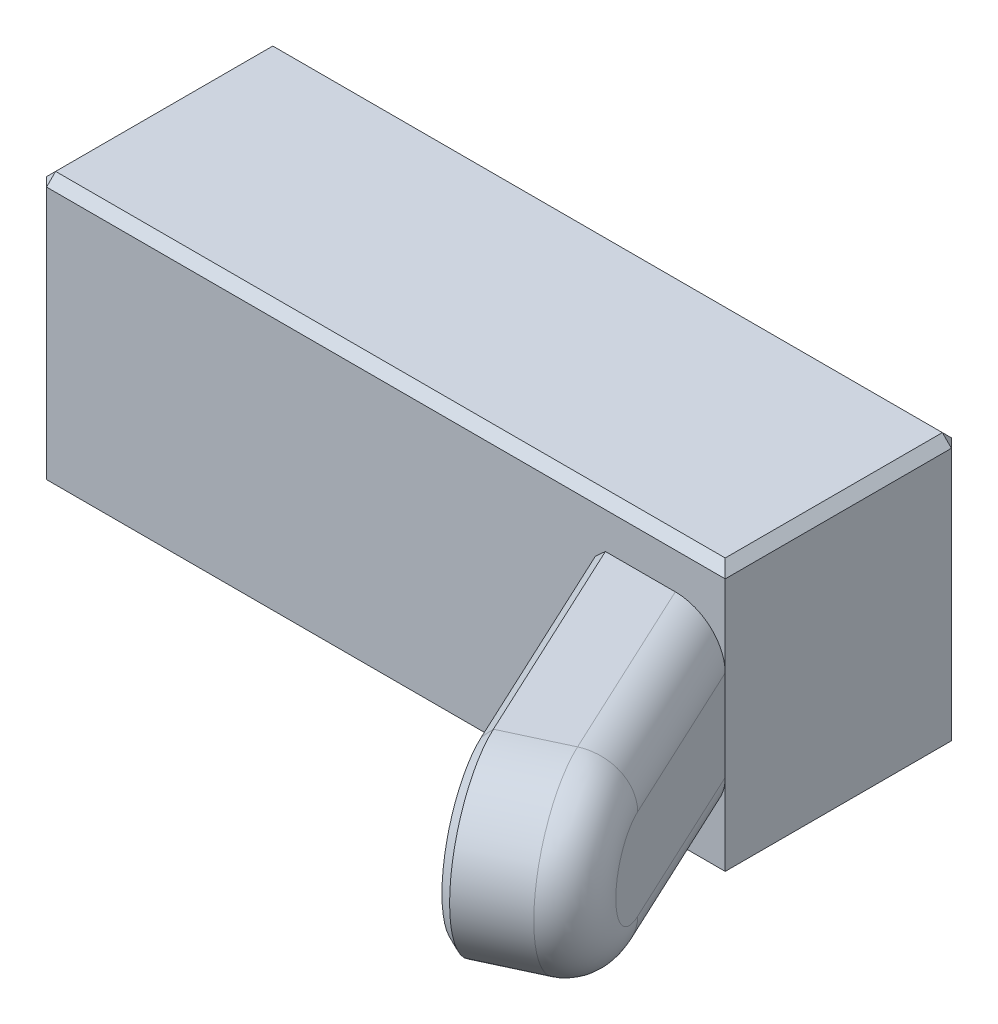
SolidWorks part; units mm, degrees
ref_plane "Front Plane" through (0, 0, 0) normal (0, 0, 1) x (1, 0, 0)
ref_plane "Top Plane" through (0, 0, 0) normal (0, 1, 0) x (1, 0, 0)
ref_plane "Right Plane" through (0, 0, 0) normal (1, 0, 0) x (0, 0, -1)
sketch "Sketch1" plane through (0, 0, 0) normal (0, 1, 0) x (1, 0, 0)
  line L1 (38, -13) -> (-38, -13)
  line L2 (38, -13) -> (38, 13)
  line L3 (38, 13) -> (-38, 13)
  line L4 (-38, -13) -> (-38, 13)
  line L5 (38, -13) -> (-38, 13) construction
  line L6 (38, 13) -> (-38, -13) construction
  point P0 (0, 0)
  dimension "D1" = 26
  dimension "D2" = 76
extrude "Boss-Extrude1" add sketch "Sketch1" along normal blind 15 and the other way blind 15
ref_plane "Plane1" through (26.2337, 0, -12.233) normal (-0.9063, 0, 0.4226) x (0, 1, 0)
sketch "Sketch3" plane through (26.2337, 0, -12.233) normal (-0.9063, 0, 0.4226) x (0, 1, 0)
  line L0 (-10, -27.8415) -> (-10, -47.8415)
  line L1 (-15, -27.8415) -> (15, -27.8415) construction
  line L2 (0, -1000.4541) -> (0, 48999.5459) construction
  line L3 (-10, -27.8415) -> (10, -27.8415)
  line L4 (10, -27.8415) -> (10, -47.8415)
  arc A0 (-10, -47.8415) -> (10, -47.8415) centre (0, -47.8415) ccw
  point P11 (0, -27.8415)
  point P13 (0, -57.8415)
  dimension "D1" = 20
  dimension "D2" = 30
extrude "Boss-Extrude2" add sketch "Sketch3" along normal blind 13 separate body
sketch "Sketch4" plane through (11.7663, 0, 25.233) normal (-0.4226, 0, -0.9063) x (-0.9063, 0, 0.4226)
  line L4 (-28.9457, 10) -> (-28.9457, -10)
  line L5 (-28.9457, -10) -> (-15.9457, -10)
  line L6 (-15.9457, -10) -> (-15.9457, 10)
  line L7 (-15.9457, 10) -> (-28.9457, 10)
  line L8 (-28.9457, 10) -> (-28.9457, -10)
  line L9 (-28.9457, -10) -> (-15.9457, -10)
  line L10 (-15.9457, -10) -> (-15.9457, 10)
  line L11 (-15.9457, 10) -> (-28.9457, 10)
  dimension "D1" = 0
extrude "Boss-Extrude3" add sketch "Sketch4" along normal up to next
fillet "Fillet1" radius 5 3 edges at (42.2262, -10, 22.0631) (50.6785, 0, 40.1892) (42.2262, 10, 22.0631)
chamfer "Chamfer1" distance 1 angle 45 14 edges at (-38, 0, -13) (-38, 0, 13) (0, -15, 13) (38, -15, 0) (-38, -15, 0) (0, -15, -13) (0, 15, -13) (-38, 15, 0) (0, 15, 13) (38, 15, 0) (38, 0, -13) (29.1632, -10, 24.8101) (38.8965, 0, 45.6833) (29.1632, 10, 24.8101)
sketch "Sketch5" plane through (0, -15, 0) normal (0, -1, 0) x (1, 0, 0)
  line L0 (-38, -12) -> (-38, 12) construction
  circle A0 centre (-28, 0) radius 5
  dimension "D1" = 10
  dimension "D2" = 10
extrude "Boss-Extrude4" add sketch "Sketch5" along normal blind 2 contours A0
